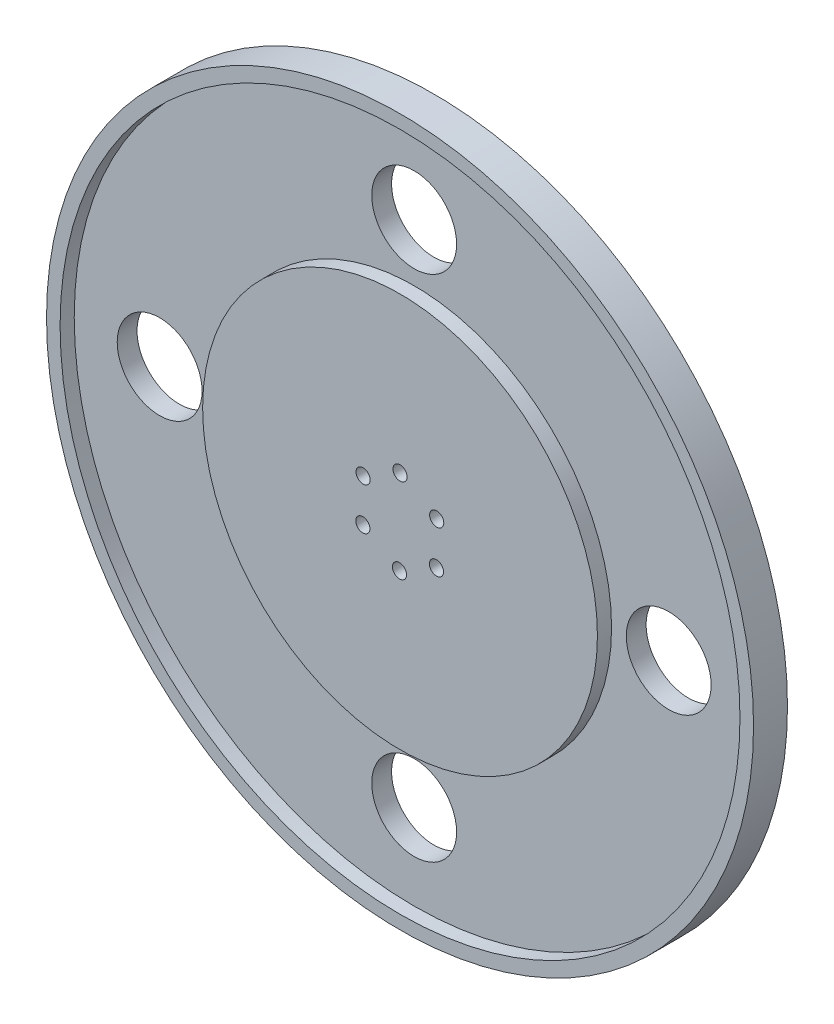
SolidWorks part; units mm, degrees
ref_plane "Front Plane" through (0, 0, 0) normal (0, 0, 1) x (1, 0, 0)
ref_plane "Top Plane" through (0, 0, 0) normal (0, 1, 0) x (1, 0, 0)
ref_plane "Right Plane" through (0, 0, 0) normal (1, 0, 0) x (0, 0, -1)
sketch "Sketch1" plane through (0, 0, 0) normal (0, 0, 1) x (1, 0, 0)
  circle A0 centre (0, 0) radius 79.375
  circle A1 centre (0, 0) radius 76.327
  circle A2 centre (0, 0) radius 44.323
  dimension "D1" = 158.75
  dimension "D2" = 152.654
  dimension "D3" = 88.646
extrude "Boss-Extrude1" add sketch "Sketch1" along normal blind 7.62 contours A2 | A0 A1 region at (-77.1299, 0, 0) region at (0, 0, 0)
extrude "Boss-Extrude2" add sketch "Sketch1<3>" along normal blind 4.445 contours A1 A2 region at (-74.1681, 0, 0)
sketch "Sketch1<3>" plane through (0, 0, 0) normal (0, 0, 1) x (1, 0, 0) same geometry as "Sketch1"
sketch "Sketch2" plane through (0, 0, 0) normal (0, 0, -1) x (-1, 0, 0)
  circle A0 centre (0, 0) radius 57.15
  circle A1 centre (0, 57.15) radius 9.525
  circle A2 centre (57.15, 0) radius 9.525
  circle A3 centre (0, -57.15) radius 9.525
  circle A4 centre (-57.15, 0) radius 9.525
  point P14 (0, 0)
  dimension "D1" = 114.3
  dimension "D2" = 4
  dimension "D3" = 19.05
extrude "Cut-Extrude1" cut sketch "Sketch2" against normal up to next contours A0 A1 | A0 A1 | A0 A4 | A0 A4 | A0 A3 | A0 A3 | A0 A2 | A0 A2 region at (-52.9679, 0, 0) region at (-61.0462, 0, 0) region at (0, 52.9679, 0) region at (0, 61.0462, 0) region at (0, -61.0462, 0) region at (0, -52.9679, 0) region at (52.9679, 0, 0) region at (61.0462, 0, 0)
sketch "Sketch3" plane through (0, 0, 0) normal (0, 0, -1) x (-1, 0, 0)
  circle A0 centre (0, 0) radius 13.0556
  dimension "D1" = 26.1112
sketch "Sketch4" plane through (0, 0, 0) normal (0, 0, -1) x (-1, 0, 0)
  arc A0 (1.5819, 9.367) -> (-7.3617, 6.004) centre (0, 0) ccw
  circle A1 centre (0, 9.4996) radius 1.5875
  circle A2 centre (8.293, 4.7815) radius 1.5875
  circle A3 centre (8.3535, -4.7596) radius 1.5875
  circle A4 centre (0.121, -9.5825) radius 1.5875
  circle A5 centre (-8.172, -4.8643) radius 1.5875
  circle A6 centre (-8.2325, 4.6767) radius 1.5875
  arc A7 (7.3296, 6.0432) -> (-1.5819, 9.367) centre (0, 0) ccw
  arc A8 (8.9171, -3.2755) -> (8.9022, 3.3155) centre (0, 0) ccw
  arc A9 (1.6911, -9.3479) -> (7.3641, -6.001) centre (0, 0) ccw
  arc A10 (-7.2404, -6.1497) -> (-1.4545, -9.3876) centre (0, 0) ccw
  arc A11 (-8.9267, 3.249) -> (-8.8578, -3.4326) centre (0, 0) ccw
  point P16 (-1.5478, -1.2615)
  point P26 (0, 0)
  dimension "D1" = 18.9992
  dimension "D2" = 3.175
extrude "Cut-Extrude2" cut sketch "Sketch4" against normal up to next contours A0 A1 | A0 A1 | A2 | A3 | A4 | A5 | A6 region at (0, 8.8025, 0) region at (0, 10.1489, 0) region at (-8.293, 4.7815, 0) region at (8.2325, 4.6767, 0) region at (-8.3535, -4.7596, 0) region at (8.172, -4.8643, 0) region at (-0.121, -9.5825, 0)
